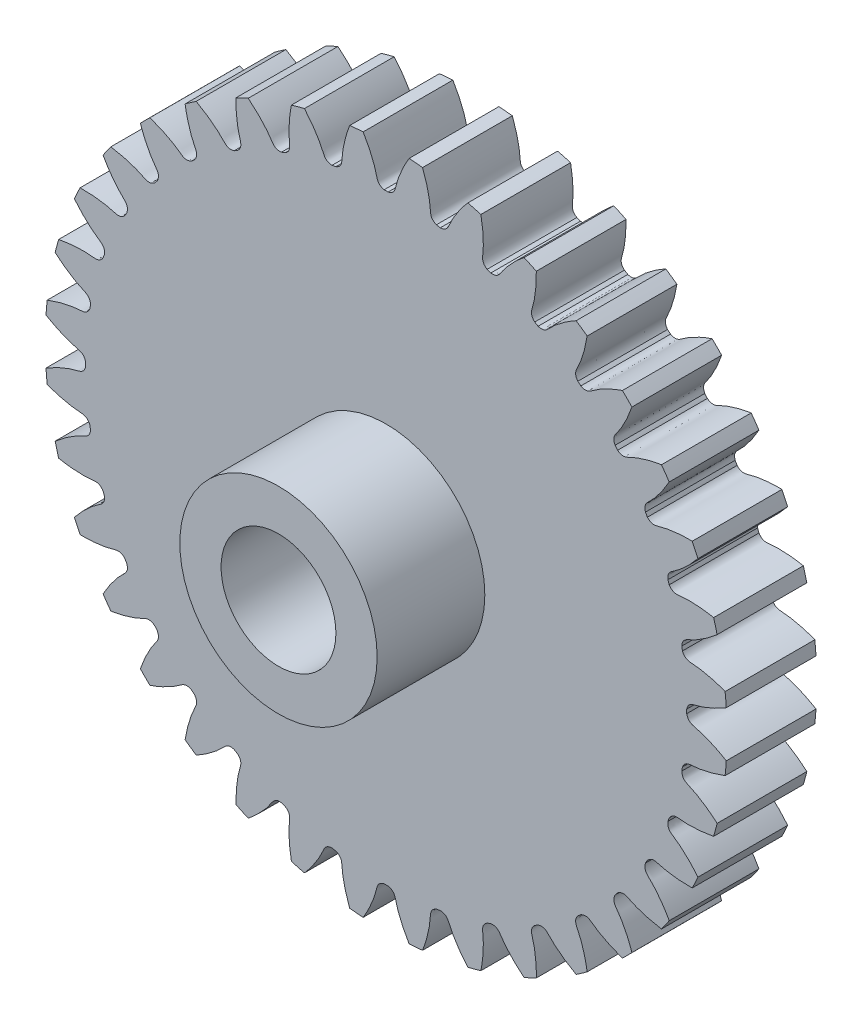
SolidWorks part; units mm, degrees
ref_plane "前视基准面" through (0, 0, 0) normal (0, 0, 1) x (1, 0, 0)
ref_plane "上视基准面" through (0, 0, 0) normal (0, 1, 0) x (1, 0, 0)
ref_plane "右视基准面" through (0, 0, 0) normal (1, 0, 0) x (0, 0, -1)
other "Configuration Table"
sketch "草图1" plane through (0, 0, 0) normal (0, 0, 1) x (1, 0, 0)
  circle A0 centre (0, 0) radius 9.5
extrude "凸台-拉伸1" add sketch "草图1" along normal blind 2.5
ref_axis "基准轴1" through (0, 0, 2.5) along (0, 0, -1)
sketch "草图2" plane through (0, 0, 0) normal (0, 0, 1) x (1, 0, 0)
  line L0 (0, 0) -> (0, 9.5) construction
  circle A0 centre (0, 0) radius 9.5 construction
  arc A1 (0.0549, 8.3748) -> (-0.0549, 8.3748) centre (0, 0) ccw
  arc A2 (1.757, 10.7884) -> (-1.757, 10.7884) centre (0, 0) ccw
  spline S0 degree 3 poles (0.0549, 8.3748) (0.235, 8.4152) (0.2505, 8.5493) (0.2882, 8.6914) (0.2997, 8.7319) (0.3131, 8.7753) (0.3284, 8.8217) (0.3457, 8.871) (0.3652, 8.9231) (0.3869, 8.9779) (0.4111, 9.0354) (0.4378, 9.0956) (0.4671, 9.1582) (0.4992, 9.2232) (0.5341, 9.2907) (0.5719, 9.3603) (0.6128, 9.4322) (0.6569, 9.5061) (0.7043, 9.582) (0.755, 9.6598) (0.8091, 9.7393) (0.8668, 9.8205) (0.9281, 9.9032) (0.9931, 9.9874) (1.0619, 10.0729) (1.1346, 10.1596) (1.2112, 10.2474) (1.2919, 10.3361) (1.3766, 10.4256) (1.4655, 10.5159) (1.5912, 10.6386) (1.6895, 10.7288) (1.757, 10.7884) knots 0 0 0 0 0.120371 0.133303 0.147364 0.162556 0.178878 0.19633 0.214913 0.234626 0.255469 0.277443 0.300547 0.324782 0.350146 0.376641 0.404267 0.433023 0.462909 0.493925 0.526072 0.559349 0.593757 0.629294 0.665963 0.703761 0.74269 0.782749 0.823939 0.866258 0.909709 1 1 1 1
  spline S1 degree 3 poles (-0.0549, 8.3748) (-0.235, 8.4152) (-0.2505, 8.5493) (-0.2882, 8.6914) (-0.2997, 8.7319) (-0.3131, 8.7753) (-0.3284, 8.8217) (-0.3457, 8.871) (-0.3652, 8.9231) (-0.3869, 8.9779) (-0.4111, 9.0354) (-0.4378, 9.0956) (-0.4671, 9.1582) (-0.4992, 9.2232) (-0.5341, 9.2907) (-0.5719, 9.3603) (-0.6128, 9.4322) (-0.6569, 9.5061) (-0.7043, 9.582) (-0.755, 9.6598) (-0.8091, 9.7393) (-0.8668, 9.8205) (-0.9281, 9.9032) (-0.9931, 9.9874) (-1.0619, 10.0729) (-1.1346, 10.1596) (-1.2112, 10.2474) (-1.2919, 10.3361) (-1.3766, 10.4256) (-1.4655, 10.5159) (-1.5912, 10.6386) (-1.6895, 10.7288) (-1.757, 10.7884) knots 0 0 0 0 0.120371 0.133303 0.147364 0.162556 0.178878 0.19633 0.214913 0.234626 0.255469 0.277443 0.300547 0.324782 0.350146 0.376641 0.404267 0.433023 0.462909 0.493925 0.526072 0.559349 0.593757 0.629294 0.665963 0.703761 0.74269 0.782749 0.823939 0.866258 0.909709 1 1 1 1
extrude "切除-拉伸1" cut sketch "草图2" along normal through all
pattern_circular "阵列(圆周)1" count 36 every 10 about axis through (0, 0, 2.5) along (0, 0, -1) of "切除-拉伸1"
sketch "草图3" plane through (0, 0, 0) normal (0, 0, 1) x (1, 0, 0)
  circle A0 centre (0, 0) radius 9 construction
  dimension "Dn" = 18
sketch "草图4" plane through (0, 0, 0) normal (0, 0, -1) x (-1, 0, 0)
  circle A0 centre (0, 0) radius 2.75
  dimension "D1" = 5.5
extrude "凸台-拉伸2" add sketch "草图4" against normal offset from surface (5.5 mm away) 3 up to face at (0, 0, 2.5) offset beyond the face yes
sketch "草图5" plane through (0, 0, 5.5) normal (0, 0, 1) x (1, 0, 0)
  circle A0 centre (0, 0) radius 1.6
  dimension "D1" = 3.2
extrude "切除-拉伸2" cut sketch "草图5" against normal up to next
